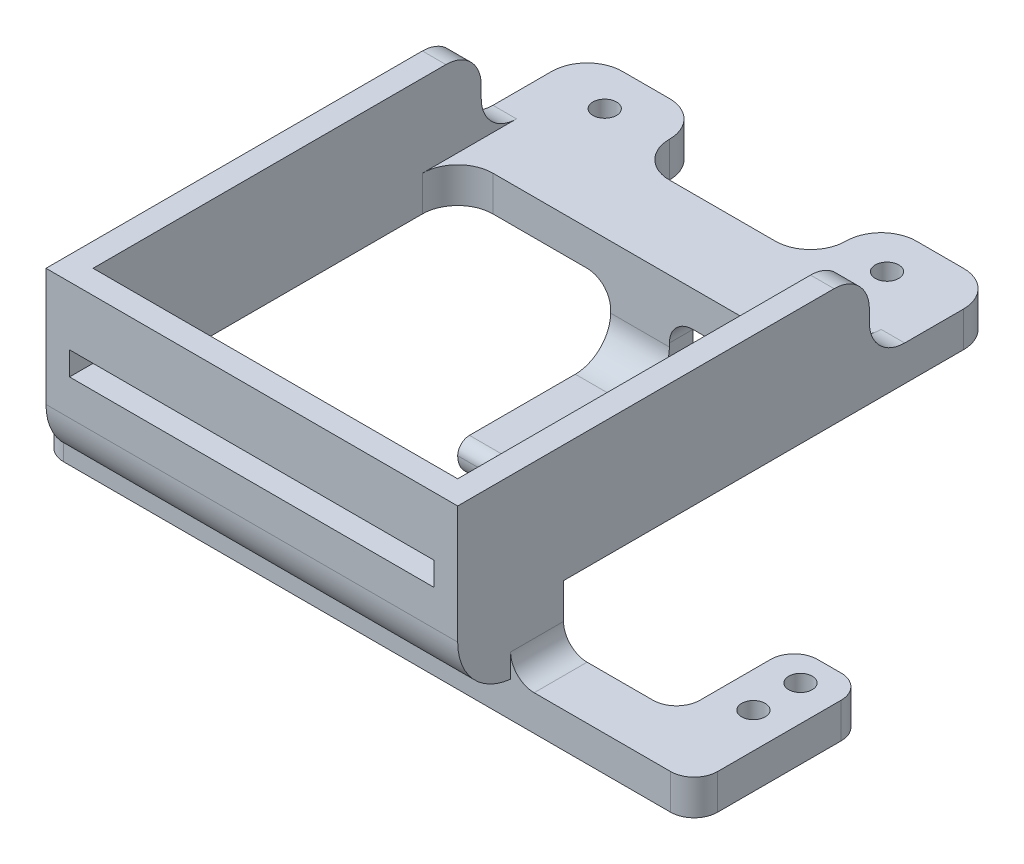
SolidWorks part; units mm, degrees
material "聚脂树脂"
ref_plane "前视基准面" through (0, 0, 0) normal (0, 0, 1) x (1, 0, 0)
ref_plane "上视基准面" through (0, 0, 0) normal (0, 1, 0) x (1, 0, 0)
ref_plane "右视基准面" through (0, 0, 0) normal (1, 0, 0) x (0, 0, -1)
other "Configuration Table"
sketch "草图1" plane through (0, 0, 0) normal (0, 1, 0) x (1, 0, 0)
  line L1 (-15.5, -15.5) -> (15.5, -15.5)
  line L2 (-15.5, -15.5) -> (-15.5, 15.5)
  line L3 (-15.5, 15.5) -> (15.5, 15.5)
  line L4 (15.5, -15.5) -> (15.5, 15.5)
  line L5 (-15.5, -15.5) -> (15.5, 15.5) construction
  line L6 (-15.5, 15.5) -> (15.5, -15.5) construction
  line L7 (-17.5, -17.5) -> (17.5, -17.5)
  line L8 (-17.5, -17.5) -> (-17.5, 17.5)
  line L9 (-17.5, 17.5) -> (17.5, 17.5)
  line L10 (17.5, -17.5) -> (17.5, 17.5)
  line L11 (-17.5, -17.5) -> (17.5, 17.5) construction
  line L12 (-17.5, 17.5) -> (17.5, -17.5) construction
  point P0 (0, 0)
  point P6 (0, 0)
  dimension "D1" = 31
  dimension "D2" = 35
  dimension "D3" = 31
  dimension "D4" = 35
extrude "凸台-拉伸1" add sketch "草图1" along normal blind 10
sketch "草图2" plane through (0, 0, 0) normal (0, -1, 0) x (1, 0, 0)
  line L0 (0, 0) -> (22.2285, 0) construction
  line L1 (15.5, 8.5) -> (17.5, 8.5)
  line L2 (15.5, 15.5) -> (15.5, -15.5) construction
  line L3 (17.5, 17.5) -> (17.5, -17.5) construction
  line L4 (17.5, 8.5) -> (17.5, 17.5)
  line L5 (17.5, 17.5) -> (-17.5, 17.5)
  line L6 (-17.5, 17.5) -> (-17.5, 8.5)
  line L7 (-17.5, -17.5) -> (-17.5, 17.5) construction
  line L8 (-17.5, 8.5) -> (15.5, 8.5)
  dimension "D1" = 8.5
extrude "凸台-拉伸2" add sketch "草图2" along normal blind 5
sketch "草图3" plane through (0, 0, -17.5) normal (0, 0, -1) x (-1, 0, 0)
  line L0 (-15.5, 10) -> (15.5, 10)
  line L1 (-17.5, 10) -> (17.5, 10) construction
  line L2 (15.5, 10) -> (15.5, 3)
  line L3 (15.5, 3) -> (-15.5, 3)
  line L4 (0, 0) -> (0, 13.5695) construction
  line L5 (-15.5, 10) -> (-15.5, 3)
  point P10 (0, 10)
  dimension "D1" = 7
  dimension "D2" = 31
extrude "切除-拉伸1" cut sketch "草图3" against normal blind 3
sketch "草图4" plane through (0, -5, 0) normal (0, -1, 0) x (1, 0, 0)
  line L0 (17.5, 8.5) -> (17.5, 13)
  line L1 (17.5, 8.5) -> (17.5, 17.5) construction
  line L2 (17.5, 13) -> (33.1, 13)
  line L3 (33.1, 13) -> (33.1, 8.5)
  line L4 (33.1, 8.5) -> (17.5, 8.5)
  line L5 (-17.5, 8.5) -> (-17.5, 13)
  line L6 (-17.5, 17.5) -> (-17.5, 8.5) construction
  line L7 (-17.5, 13) -> (-22.5, 13)
  line L8 (-22.5, 13) -> (-22.5, 8.5)
  line L9 (-22.5, 8.5) -> (-17.5, 8.5)
  line L10 (-17.5, 13) -> (17.5, 13)
  line L11 (-17.5, 8.5) -> (17.5, 8.5)
  line L12 (0, 0) -> (39.5915, 0) construction
  line L13 (30.1, 0) -> (30.1, 21.221) construction
  line L14 (-19.7, 0) -> (-19.7, 23.9657) construction
  line L15 (27.1, 8.5) -> (27.1, -1.5)
  line L16 (27.1, -1.5) -> (33.1, -1.5)
  line L17 (33.1, -1.5) -> (33.1, 8.5)
  line L18 (-22.5, 8.5) -> (-22.5, 2.5)
  line L19 (-22.5, 2.5) -> (-17.5, 2.5)
  line L20 (-17.5, 2.5) -> (-17.5, 8.5)
  circle A0 centre (30.1, 4.96) radius 1
  circle A1 centre (-19.7, 5.46) radius 1
  circle A2 centre (30.1, 0.96) radius 1
  line M5 (-17.5, 8.5) -> (17.5, 8.5)
  line M6 (17.5, 8.5) -> (17.5, 17.5)
  line M8 (-17.5, 17.5) -> (-17.5, 8.5)
  dimension "D5" = 2
  dimension "D6" = 2
  dimension "D9" = 2
  dimension "D10" = 4
  dimension "D14" = 6
  dimension "D1" = 2.2
  dimension "D2" = 12.6
  dimension "D3" = 15.6
  dimension "D4" = 5
  dimension "D7" = 7.54
  dimension "D8" = 8.04
  dimension "D11" = 6
  dimension "D12" = 10
  dimension "D13" = 5
extrude "凸台-拉伸3" add sketch "草图4" along normal blind 3 contours L8 L9 L7 M8 | L10 M8 M5 M6 | L19 L20 L9 L18 A1 | L4 L3 L2 M6 | L16 L17 L4 L15 A2 A0 region at (0, -5, 10.75) region at (25.3, -5, 10.75) region at (30.1, -5, 3.5632) region at (-20, -5, 10.75) region at (-17.5781, -5, 5.5)
fillet "圆角2" radius 2 8 edges at (33.1, -6.5, -1.5) (27.1, -6.5, -1.5) (-17.5, -6.5, 2.5) (-22.5, -6.5, 2.5) (33.1, -6.5, 13) (-22.5, -6.5, 13) (-17.5, -6.5, 8.5) (27.1, -6.5, 8.5)
fillet "圆角3" radius 2 2 edges at (17.5, -5, 10.75) (-17.5, -5, 10.75)
sketch "草图5" plane through (0, 0, 0) normal (0, -1, 0) x (1, 0, 0)
  line L0 (-2.5, -15.5) -> (2.5, -15.5)
  line L1 (15.5, -15.5) -> (-15.5, -15.5) construction
  line L2 (2.5, -15.5) -> (2.5, -17.5)
  line L3 (17.5, -17.5) -> (-17.5, -17.5) construction
  line L4 (2.5, -17.5) -> (-2.5, -17.5)
  line L5 (0, -17.5) -> (0, -1.9044) construction
  line L6 (-2.5, -15.5) -> (-2.5, -17.5)
  point P12 (0, -15.5)
  dimension "D1" = 5
extrude "凸台-拉伸4" add sketch "草图5" along normal blind 8.3
sketch "草图6" plane through (0, -8.3, 0) normal (0, -1, 0) x (1, 0, 0)
  line L0 (-2.5, -15.5) -> (-2.5, -2.5)
  line L1 (-2.5, -15.5) -> (2.5, -15.5)
  line L2 (2.5, -15.5) -> (2.5, -2.5)
  line L3 (2.5, -2.5) -> (-2.5, -2.5)
  dimension "D1" = 13
extrude "凸台-拉伸5" add sketch "草图6" against normal blind 3
fillet "圆角4" radius 2 2 edges at (0, -8.3, -2.5) (0, -8.3, -17.5)
fillet "圆角5" radius 1 1 edges at (0, -5.3, -2.5)
fillet "圆角6" radius 2 2 edges at (2.5, 0, -16.5) (-2.5, 0, -16.5)
sketch "草图7" plane through (0, 0, 15.5) normal (0, 0, -1) x (-1, 0, 0)
  line L0 (-15.5, 3) -> (15.5, 3)
  line L1 (15.5, 3) -> (15.5, 5)
  line L2 (15.5, 10) -> (15.5, 0) construction
  line L3 (15.5, 5) -> (-15.5, 5)
  line L4 (-15.5, 10) -> (-15.5, 0) construction
  line L5 (-15.5, 5) -> (-15.5, 3)
extrude "切除-拉伸2" cut sketch "草图7" against normal blind 10
fillet "圆角7" radius 5 2 edges at (0, 0, 8.5) (0, -5, 17.5)
sketch "草图8" plane through (0, 3, 0) normal (0, 1, 0) x (1, 0, 0)
  line L0 (-0.5, 0) -> (-0.5, 37.2738) construction
  line L1 (-0.5, 0) -> (45.9139, 0) construction
  line L7 (0, 0) -> (-0.5, 0) construction
  line L8 (-17.5, 17.5) -> (-17.5, 28.5)
  line L9 (-17.5, 28.5) -> (17.5, 28.5)
  line L10 (17.5, 28.5) -> (17.5, 17.5)
  line L11 (17.5, 17.5) -> (-17.5, 17.5)
  circle A0 centre (11.5, 25) radius 1
  circle A1 centre (-12.5, 25) radius 1
  line M7 (-15.5, 15.5) -> (15.5, 15.5)
  line M9 (15.5, 17.5) -> (-15.5, 17.5)
  dimension "D1" = 2
  dimension "D2" = 24
  dimension "D4" = 25
  dimension "D3" = 0.5
  dimension "D5" = 11
extrude "凸台-拉伸6" add sketch "草图8" against normal blind 3 contours A1 A0 L10 M9 | A1 A0 M7 region at (0.0083, 3, -22.9668)
fillet "圆角8" radius 3 6 edges at (-17.5, 1.5, -28.5) (17.5, 1.5, -28.5) (16.5, 10, -17.5) (16.5, 3, -17.5) (-16.5, 10, -17.5) (-16.5, 3, -17.5)
fillet "圆角9" radius 3 2 edges at (-15.5, 1.5, -15.5) (15.5, 1.5, -15.5)
sketch "草图11" plane through (0, 0, 0) normal (0, -1, 0) x (1, 0, 0)
  line L0 (0, 0) -> (0, -31.2421) construction
  line L1 (-7.5, -28.5) -> (7.5, -28.5)
  line L2 (-14.5, -28.5) -> (14.5, -28.5) construction
  line L3 (7.5, -28.5) -> (7.5, -22.5)
  line L4 (7.5, -22.5) -> (-7.5, -22.5)
  line L5 (-7.5, -28.5) -> (-7.5, -22.5)
  point P10 (0, -22.5)
  point P11 (0, -28.5)
  dimension "D1" = 15
  dimension "D2" = 6
extrude "切除-拉伸4" cut sketch "草图11" against normal blind 3
fillet "圆角10" radius 3 4 edges at (7.5, 1.5, -28.5) (7.5, 1.5, -22.5) (-7.5, 1.5, -22.5) (-7.5, 1.5, -28.5)
fillet "圆角11" radius 3 1 edges at (0, -5.3, -15.5)
